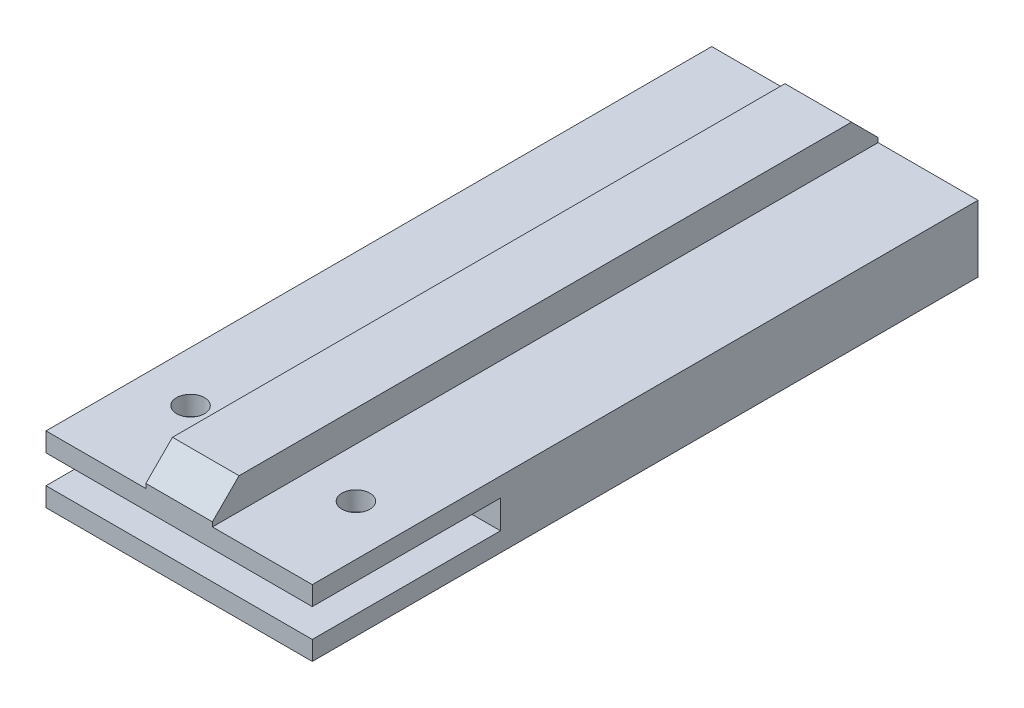
SolidWorks part; units mm, degrees
material "Cast Alloy Steel"
ref_plane "Front Plane" through (0, 0, 0) normal (0, 0, 1) x (1, 0, 0)
ref_plane "Top Plane" through (0, 0, 0) normal (0, 1, 0) x (1, 0, 0)
ref_plane "Right Plane" through (0, 0, 0) normal (1, 0, 0) x (0, 0, -1)
sketch "Sketch1" plane through (0, 0, 0) normal (0, 0, 1) x (1, 0, 0)
  line L0 (-15, -7.5) -> (15, -7.5)
  line L1 (15, -7.5) -> (15, 0)
  line L2 (15, 0) -> (-15, 0)
  line L7 (-15, 0) -> (-15, -7.5)
  point P4 (0, 0)
  point P5 (0, -7.5)
  point P6 (0, 0)
  point P11 (0, 0)
  dimension "D1" = 7.5
  dimension "D2" = 30
extrude "Boss-Extrude1" add sketch "Sketch1" along normal blind 75
sketch "Sketch6" plane through (15, 0, 0) normal (1, 0, 0) x (0, 0, -1)
  line L0 (-75, -2.15) -> (-53.8, -2.15)
  line L1 (-75, -7.5) -> (-75, 0) construction
  line L2 (-53.8, -2.15) -> (-53.8, -5.35)
  line L3 (-53.8, -5.35) -> (-75, -5.35)
  line L5 (-75, -2.15) -> (-75, -5.35)
  dimension "D1" = 2.15
  dimension "D2" = 21.2
  dimension "D3" = 3.2
sketch "Sketch7" plane through (0, 0, 0) normal (0, 1, 0) x (1, 0, 0)
  line L0 (-15, -37.5) -> (15, -37.5) construction
  line L5 (-15, -75) -> (-15, 0) construction
  line L6 (15, -75) -> (15, 0) construction
  line L7 (0, 0) -> (0, -75) construction
  line L8 (15, -75) -> (-15, -75) construction
  line L10 (-3.75, -75) -> (3.75, -75)
  line L11 (-3.75, -75) -> (-3.75, 0)
  line L12 (-3.75, 0) -> (3.75, 0)
  line L13 (3.75, -75) -> (3.75, 0)
  line L14 (-3.75, -75) -> (3.75, 0) construction
  line L15 (-3.75, 0) -> (3.75, -75) construction
  point P11 (0, -37.5)
  dimension "D1" = 7.5
  dimension "D2" = 75
extrude "Cut-Extrude5" cut sketch "Sketch6" against normal through all
extrude "Boss-Extrude4" add sketch "Sketch7" along normal blind 3.5
sketch "Sketch8" plane through (0, 0, 0) normal (0, 1, 0) x (1, 0, 0)
  line L1 (15, -53.8) -> (3.75, -53.8)
  line L2 (15, -75) -> (15, 0) construction
  line L3 (3.75, -75) -> (3.75, 0) construction
  line L4 (15, -75) -> (3.75, -75) construction
  circle A0 centre (9.3184, -64.4) radius 1.575
  dimension "D3" = 3.15
  dimension "D1" = 21.2
  dimension "D2" = 10.6
extrude "Cut-Extrude6" cut sketch "Sketch8" against normal through all and the other way through all contours A0
mirror "Mirror1" about plane through (0, 0, 0) normal (1, 0, 0) of "Cut-Extrude6"
chamfer "Chamfer2" distance 3 angle 45 1 edges at (0, 3.5, 75)
chamfer "Chamfer3" distance 3 angle 45 1 edges at (0, 3.5, 0)
